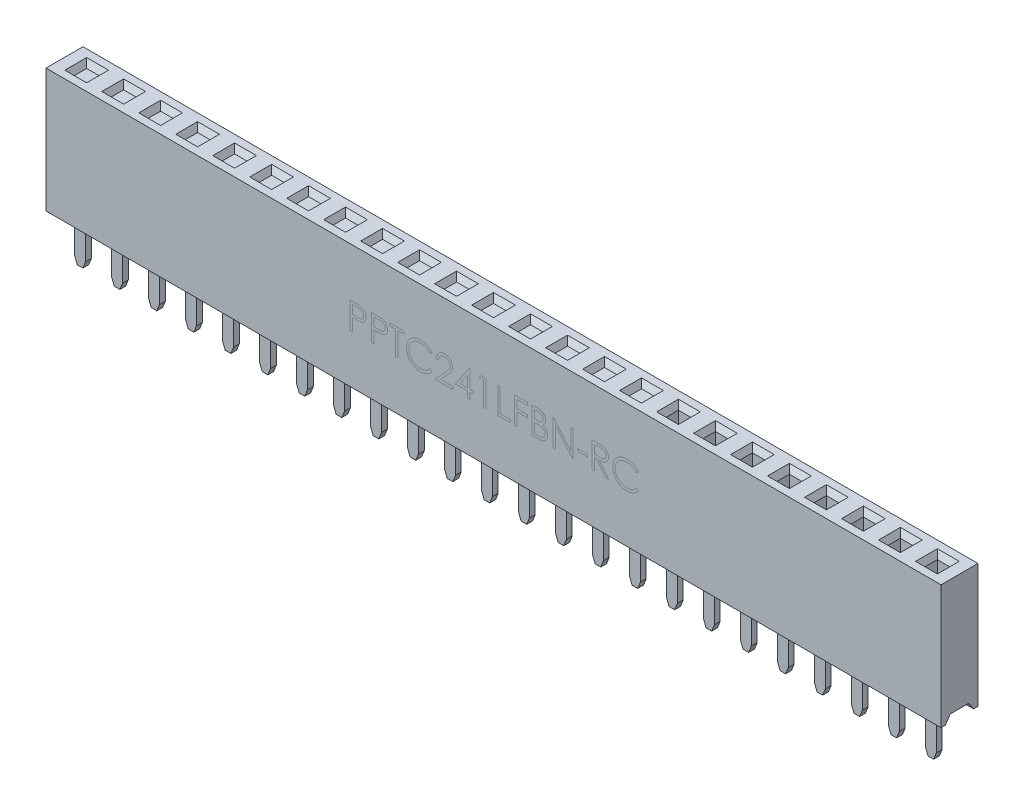
SolidWorks part; units mm, degrees
ref_plane "Front Plane" through (0, 0, 0) normal (0, 0, 1) x (1, 0, 0)
ref_plane "Top Plane" through (0, 0, 0) normal (0, 1, 0) x (1, 0, 0)
ref_plane "Right Plane" through (0, 0, 0) normal (1, 0, 0) x (0, 0, -1)
sketch "Sketch1" plane through (0, 0, 0) normal (1, 0, 0) x (0, 0, -1)
  line L0 (-1.27, 4.25) -> (1.27, 4.25)
  line L1 (1.27, 4.25) -> (1.27, -4.25)
  line L3 (0.6338, -3.75) -> (-0.6338, -3.75)
  line L5 (-1.27, -4.25) -> (-1.27, 4.25)
  line L6 (-0.6338, -3.75) -> (-1.27, -3.75) construction
  line L7 (0.6338, -3.75) -> (1.27, -3.75) construction
  line L8 (-1.27, -4.25) -> (-0.97, -4.25)
  line L9 (-0.97, -4.25) -> (-0.6338, -3.75)
  line L10 (0.6338, -3.75) -> (0.97, -4.25)
  line L11 (0.97, -4.25) -> (1.27, -4.25)
  line L12 (-0.97, -4.25) -> (0.97, -4.25) construction
  line L13 (0, -3.75) -> (0, -4.25) construction
  point P8 (0, 4.25)
  point P9 (-1.27, 0)
  dimension "D1" = 2.54
  dimension "D2" = 2.54
  dimension "D3" = 8.5
  dimension "D4" = 0.3
  dimension "D5" = 0.5
extrude "Boss-Extrude1" add sketch "Sketch1" along normal mid plane 61.46
sketch "Sketch4" plane through (0, 0, 0) normal (0, 0, 1) x (1, 0, 0)
  line L8 (30.73, -4.25) -> (-30.73, -4.25) construction
  line L11 (-30.73, 4.25) -> (-30.73, -4.25) construction
  line L16 (-29.46, -3.75) -> (-29.46, -7.45) construction
  line L17 (-29.2667, -7.45) -> (-29.6533, -7.45)
  line L18 (-29.6533, -7.45) -> (-29.835, -6.9842)
  line L19 (-29.835, -6.9842) -> (-29.835, -3.75)
  line L20 (-29.835, -3.75) -> (-29.085, -3.75)
  line L21 (-29.085, -3.75) -> (-29.085, -6.9842)
  line L22 (-29.2667, -7.45) -> (-29.085, -6.9842)
  point P0 (0, 0)
  dimension "D1" = 3.7
  dimension "D2" = 0.75
  dimension "D3" = 158.685
  dimension "D4" = 3.2342
  dimension "D5" = 0.5
  dimension "D6" = 1.27
extrude "Boss-Extrude2" add sketch "Sketch4" along normal mid plane 0.4 separate body
pattern_linear "LPattern1" count 24 spacing 2.54 along (1, 0, 0) of bodies 102 103
sketch "Sketch5" plane through (0, 4.25, 0) normal (0, 1, 0) x (1, 0, 0)
  line L0 (30.73, 1.27) -> (-30.73, 1.27) construction
  line L2 (30.73, 1.27) -> (30.73, -1.27) construction
  line L4 (28.46, 0.75) -> (29.96, 0.75)
  line L5 (28.46, 0.75) -> (28.46, -0.75)
  line L6 (28.46, -0.75) -> (29.96, -0.75)
  line L7 (29.96, 0.75) -> (29.96, -0.75)
  line L8 (28.46, 0.75) -> (29.96, -0.75) construction
  line L9 (28.46, -0.75) -> (29.96, 0.75) construction
  point P6 (29.21, 0)
  dimension "D1" = 1.52
  dimension "D2" = 1.5
  dimension "D3" = 0.52
ref_plane "Plane3" through (0, 3.85, 0) normal (0, 1, 0) x (1, 0, 0)
sketch "Sketch6" plane through (0, 3.85, 0) normal (0, 1, 0) x (1, 0, 0)
  line L8 (29.71, -0.5) -> (29.71, 0.5)
  line L9 (28.71, -0.5) -> (29.71, -0.5)
  line L10 (28.71, 0.5) -> (28.71, -0.5)
  line L11 (29.71, 0.5) -> (28.71, 0.5)
  line L12 (29.71, -0.5) -> (29.71, 0.5)
  line L13 (28.71, -0.5) -> (29.71, -0.5)
  line L14 (28.71, 0.5) -> (28.71, -0.5)
  line L15 (29.71, 0.5) -> (28.71, 0.5)
  dimension "D1" = 0.25
loft "Cut-Loft1" cut profiles "Sketch5", "Sketch6" connector at (28.46, 4.25, -0.75) connector at (28.71, 3.85, -0.5)
pattern_linear "LPattern2" count 24 spacing 2.54 along (-1, 0, 0) of "Cut-Loft1"
sketch "Sketch8" plane through (0, 3.85, 0) normal (0, 1, 0) x (1, 0, 0)
  line L0 (27.17, -0.5) -> (27.17, 0.5)
  line L1 (27.17, 0.5) -> (26.17, 0.5)
  line L2 (26.17, 0.5) -> (26.17, -0.5)
  line L3 (26.17, -0.5) -> (27.17, -0.5)
  line L4 (28.71, -0.5) -> (29.71, -0.5)
  line L5 (29.71, -0.5) -> (29.71, 0.5)
  line L6 (29.71, 0.5) -> (28.71, 0.5)
  line L7 (28.71, 0.5) -> (28.71, -0.5)
  line L8 (28.71, -0.5) -> (29.71, -0.5)
  line L9 (29.71, -0.5) -> (29.71, 0.5)
  line L10 (29.71, 0.5) -> (28.71, 0.5)
  line L11 (28.71, 0.5) -> (28.71, -0.5)
  line L12 (24.63, -0.5) -> (24.63, 0.5)
  line L13 (24.63, 0.5) -> (23.63, 0.5)
  line L14 (23.63, 0.5) -> (23.63, -0.5)
  line L15 (23.63, -0.5) -> (24.63, -0.5)
  line L16 (22.09, -0.5) -> (22.09, 0.5)
  line L17 (22.09, 0.5) -> (21.09, 0.5)
  line L18 (21.09, 0.5) -> (21.09, -0.5)
  line L19 (21.09, -0.5) -> (22.09, -0.5)
  line L20 (19.55, -0.5) -> (19.55, 0.5)
  line L21 (19.55, 0.5) -> (18.55, 0.5)
  line L22 (18.55, 0.5) -> (18.55, -0.5)
  line L23 (18.55, -0.5) -> (19.55, -0.5)
  line L24 (17.01, -0.5) -> (17.01, 0.5)
  line L25 (17.01, 0.5) -> (16.01, 0.5)
  line L26 (16.01, 0.5) -> (16.01, -0.5)
  line L27 (16.01, -0.5) -> (17.01, -0.5)
  line L28 (14.47, -0.5) -> (14.47, 0.5)
  line L29 (14.47, 0.5) -> (13.47, 0.5)
  line L30 (13.47, 0.5) -> (13.47, -0.5)
  line L31 (13.47, -0.5) -> (14.47, -0.5)
  line L32 (11.93, -0.5) -> (11.93, 0.5)
  line L33 (11.93, 0.5) -> (10.93, 0.5)
  line L34 (10.93, 0.5) -> (10.93, -0.5)
  line L35 (10.93, -0.5) -> (11.93, -0.5)
  line L36 (29.71, -0.5) -> (29.71, 0.5) construction
  dimension "D3" = 2.54
  dimension "D1" = 0
  dimension "D2" = 8
extrude "Cut-Extrude1" cut sketch "Sketch8" against normal blind 6
sketch "Sketch9" plane through (0, 0, 1.27) normal (0, 0, 1) x (1, 0, 0)
  line L0 (-30.73, -0.9) -> (30.73, -0.9) construction
  line L1 (-30.73, 4.25) -> (-30.73, -4.25) construction
  line L2 (30.73, 4.25) -> (30.73, -4.25) construction
  text T0 "PPTC241LFBN-RC" font "Century Gothic" height 1.8
  point P7 (30.73, 0)
  dimension "D1" = 0.9
wrap "Wrap1" sketch "Sketch9" wrap type scribe source sketch "Sketch9" face at (0, 0, 1.27)
